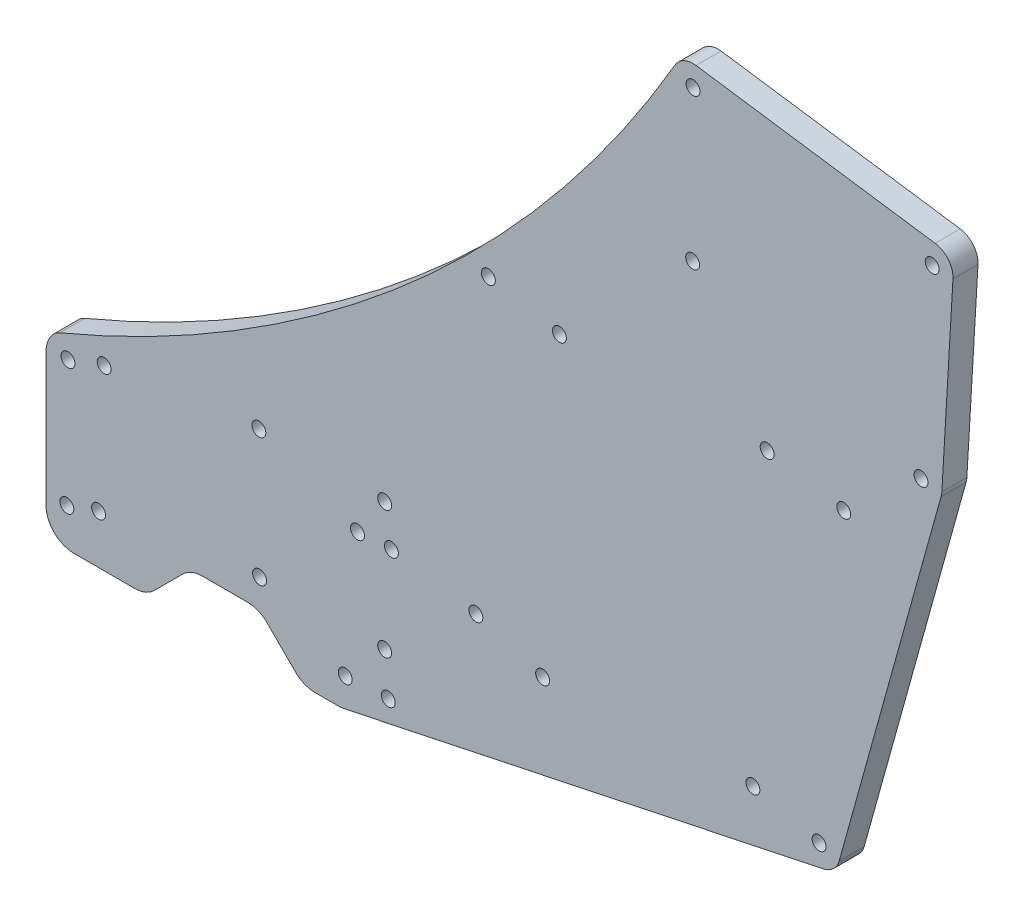
SolidWorks part; units mm, degrees
ref_plane "Front Plane" through (0, 0, 0) normal (0, 0, 1) x (1, 0, 0)
ref_plane "Top Plane" through (0, 0, 0) normal (0, 1, 0) x (1, 0, 0)
ref_plane "Right Plane" through (0, 0, 0) normal (1, 0, 0) x (0, 0, -1)
sketch "Model" plane through (0, 0, 0) normal (0, 0, 1) x (1, 0, 0)
  line L0 (-211.7059, 139.5585) -> (211.7058, 139.5585)
  line L1 (211.7058, 139.5585) -> (122.9838, -139.5584)
  line L2 (122.9838, -139.5584) -> (-211.7059, -139.5584)
  line L3 (-211.7059, -139.5584) -> (-211.7059, 139.5585)
  line L4 (-183.9889, -135.0098) -> (-175.7383, -135.0098)
  line L5 (-175.7383, -135.0098) -> (-175.7383, -139.5584)
  line L6 (-175.7383, -139.5584) -> (-183.9889, -139.5584)
  line L7 (-183.9889, -139.5584) -> (-183.9889, -135.0098)
  line L8 (5.1137, -131.3253) -> (16.7271, -131.3253)
  line L9 (16.7271, -131.3253) -> (16.7271, -139.5584)
  line L10 (16.7271, -139.5584) -> (5.1137, -139.5584)
  line L11 (5.1137, -139.5584) -> (5.1137, -131.3253)
  line L12 (-120.7856, -123.5542) -> (-97.2926, -123.5542)
  line L13 (-97.2926, -123.5542) -> (-97.2926, -126.7942)
  line L14 (-97.2926, -126.7942) -> (-120.7856, -126.7942)
  line L15 (-120.7856, -126.7942) -> (-120.7856, -123.5542)
  line L16 (-130.4136, -13.1631) -> (-127.7548, -13.1631)
  line L17 (-127.7548, -13.1631) -> (-127.7548, -110.9397)
  line L18 (-127.7548, -110.9397) -> (-130.4136, -110.9397)
  line L19 (-130.4136, -110.9397) -> (-130.4136, -13.1631)
  spline S0 degree 3 poles (121.2808, 104.4697) (121.2808, 103.8066) (121.0175, 103.1708) (120.5486, 102.7019) knots 0 0 0 0 1 1 1 1
  spline S1 degree 3 poles (120.5486, 102.7019) (120.0798, 102.2331) (119.4439, 101.9697) (118.7809, 101.9697) knots 0 0 0 0 1 1 1 1
  spline S2 degree 3 poles (118.7809, 101.9697) (117.4002, 101.9697) (116.2809, 103.089) (116.2809, 104.4697) knots 0 0 0 0 1 1 1 1
  spline S3 degree 3 poles (116.2809, 104.4697) (116.2809, 105.8504) (117.4002, 106.9696) (118.7809, 106.9696) knots 0 0 0 0 1 1 1 1
  spline S4 degree 3 poles (118.7809, 106.9696) (119.4439, 106.9696) (120.0798, 106.7062) (120.5486, 106.2374) knots 0 0 0 0 1 1 1 1
  spline S5 degree 3 poles (120.5486, 106.2374) (121.0175, 105.7686) (121.2808, 105.1327) (121.2808, 104.4697) knots 0 0 0 0 1 1 1 1
  spline S6 degree 3 poles (117.2766, 36.0936) (117.2766, 34.7129) (116.1574, 33.5937) (114.7767, 33.5937) knots 0 0 0 0 1 1 1 1
  spline S7 degree 3 poles (114.7767, 33.5937) (113.396, 33.5937) (112.2767, 34.7129) (112.2767, 36.0936) knots 0 0 0 0 1 1 1 1
  spline S8 degree 3 poles (112.2767, 36.0936) (112.2767, 37.4743) (113.396, 38.5936) (114.7767, 38.5936) knots 0 0 0 0 1 1 1 1
  spline S9 degree 3 poles (114.7767, 38.5936) (116.1574, 38.5936) (117.2766, 37.4743) (117.2766, 36.0936) knots 0 0 0 0 1 1 1 1
  spline S10 degree 3 poles (61.9275, 17.0977) (61.9275, 15.717) (60.8082, 14.5977) (59.4275, 14.5977) knots 0 0 0 0 1 1 1 1
  spline S11 degree 3 poles (59.4275, 14.5977) (58.0468, 14.5977) (56.9275, 15.717) (56.9275, 17.0977) knots 0 0 0 0 1 1 1 1
  spline S12 degree 3 poles (56.9275, 17.0977) (56.9275, 18.4784) (58.0468, 19.5976) (59.4275, 19.5976) knots 0 0 0 0 1 1 1 1
  spline S13 degree 3 poles (59.4275, 19.5976) (60.8082, 19.5976) (61.9275, 18.4784) (61.9275, 17.0977) knots 0 0 0 0 1 1 1 1
  spline S14 degree 3 poles (35.1266, 62.7496) (35.1266, 61.3689) (34.0074, 60.2496) (32.6267, 60.2496) knots 0 0 0 0 1 1 1 1
  spline S15 degree 3 poles (32.6267, 60.2496) (31.246, 60.2496) (30.1267, 61.3689) (30.1267, 62.7496) knots 0 0 0 0 1 1 1 1
  spline S16 degree 3 poles (30.1267, 62.7496) (30.1267, 64.1303) (31.246, 65.2496) (32.6267, 65.2496) knots 0 0 0 0 1 1 1 1
  spline S17 degree 3 poles (32.6267, 65.2496) (34.0074, 65.2496) (35.1266, 64.1303) (35.1266, 62.7496) knots 0 0 0 0 1 1 1 1
  spline S18 degree 3 poles (35.2798, 116.8664) (35.2798, 115.4857) (34.1605, 114.3664) (32.7798, 114.3664) knots 0 0 0 0 1 1 1 1
  spline S19 degree 3 poles (32.7798, 114.3664) (31.3991, 114.3664) (30.2798, 115.4857) (30.2798, 116.8664) knots 0 0 0 0 1 1 1 1
  spline S20 degree 3 poles (30.2798, 116.8664) (30.2798, 117.5294) (30.5432, 118.1653) (31.0121, 118.6341) knots 0 0 0 0 1 1 1 1
  spline S21 degree 3 poles (31.0121, 118.6341) (31.4809, 119.103) (32.1168, 119.3664) (32.7798, 119.3664) knots 0 0 0 0 1 1 1 1
  spline S22 degree 3 poles (32.7798, 119.3664) (33.4428, 119.3664) (34.0787, 119.103) (34.5475, 118.6341) knots 0 0 0 0 1 1 1 1
  spline S23 degree 3 poles (34.5475, 118.6341) (35.0164, 118.1653) (35.2798, 117.5294) (35.2798, 116.8664) knots 0 0 0 0 1 1 1 1
  spline S24 degree 3 poles (56.804, -89.9943) (56.804, -91.375) (55.6847, -92.4943) (54.304, -92.4943) knots 0 0 0 0 1 1 1 1
  spline S25 degree 3 poles (54.304, -92.4943) (52.9233, -92.4943) (51.804, -91.375) (51.804, -89.9943) knots 0 0 0 0 1 1 1 1
  spline S26 degree 3 poles (51.804, -89.9943) (51.804, -88.6136) (52.9233, -87.4943) (54.304, -87.4943) knots 0 0 0 0 1 1 1 1
  spline S27 degree 3 poles (54.304, -87.4943) (55.6847, -87.4943) (56.804, -88.6136) (56.804, -89.9943) knots 0 0 0 0 1 1 1 1
  spline S28 degree 3 poles (80.6115, -95.7304) (80.6115, -97.1111) (79.4922, -98.2304) (78.1115, -98.2304) knots 0 0 0 0 1 1 1 1
  spline S29 degree 3 poles (78.1115, -98.2304) (76.7308, -98.2304) (75.6115, -97.1111) (75.6115, -95.7304) knots 0 0 0 0 1 1 1 1
  spline S30 degree 3 poles (75.6115, -95.7304) (75.6115, -94.3497) (76.7308, -93.2304) (78.1115, -93.2304) knots 0 0 0 0 1 1 1 1
  spline S31 degree 3 poles (78.1115, -93.2304) (79.4922, -93.2304) (80.6115, -94.3497) (80.6115, -95.7304) knots 0 0 0 0 1 1 1 1
  spline S32 degree 3 poles (-189.541, -80.3042) (-189.541, -81.6849) (-190.6603, -82.8042) (-192.041, -82.8042) knots 0 0 0 0 1 1 1 1
  spline S33 degree 3 poles (-192.041, -82.8042) (-193.4217, -82.8042) (-194.5409, -81.6849) (-194.5409, -80.3042) knots 0 0 0 0 1 1 1 1
  spline S34 degree 3 poles (-194.5409, -80.3042) (-194.5409, -78.9235) (-193.4217, -77.8043) (-192.041, -77.8043) knots 0 0 0 0 1 1 1 1
  spline S35 degree 3 poles (-192.041, -77.8043) (-190.6603, -77.8043) (-189.541, -78.9235) (-189.541, -80.3042) knots 0 0 0 0 1 1 1 1
  spline S36 degree 3 poles (-85.4284, -81.8636) (-85.4284, -82.5266) (-85.6918, -83.1625) (-86.1606, -83.6313) knots 0 0 0 0 1 1 1 1
  spline S37 degree 3 poles (-86.1606, -83.6313) (-86.6295, -84.1001) (-87.2654, -84.3635) (-87.9284, -84.3635) knots 0 0 0 0 1 1 1 1
  spline S38 degree 3 poles (-87.9284, -84.3635) (-88.5914, -84.3635) (-89.2273, -84.1001) (-89.6961, -83.6313) knots 0 0 0 0 1 1 1 1
  spline S39 degree 3 poles (-89.6961, -83.6313) (-90.165, -83.1625) (-90.4284, -82.5266) (-90.4284, -81.8636) knots 0 0 0 0 1 1 1 1
  spline S40 degree 3 poles (-90.4284, -81.8636) (-90.4284, -80.4829) (-89.3091, -79.3636) (-87.9284, -79.3636) knots 0 0 0 0 1 1 1 1
  spline S41 degree 3 poles (-87.9284, -79.3636) (-86.5477, -79.3636) (-85.4284, -80.4829) (-85.4284, -81.8636) knots 0 0 0 0 1 1 1 1
  spline S42 degree 3 poles (-73.2184, -81.251) (-73.2184, -82.6317) (-74.3377, -83.7509) (-75.7183, -83.7509) knots 0 0 0 0 1 1 1 1
  spline S43 degree 3 poles (-75.7183, -83.7509) (-76.3814, -83.7509) (-77.0173, -83.4875) (-77.4861, -83.0187) knots 0 0 0 0 1 1 1 1
  spline S44 degree 3 poles (-77.4861, -83.0187) (-77.9549, -82.5499) (-78.2183, -81.914) (-78.2183, -81.251) knots 0 0 0 0 1 1 1 1
  spline S45 degree 3 poles (-78.2183, -81.251) (-78.2183, -80.5879) (-77.9549, -79.9521) (-77.4861, -79.4832) knots 0 0 0 0 1 1 1 1
  spline S46 degree 3 poles (-77.4861, -79.4832) (-77.0173, -79.0144) (-76.3814, -78.751) (-75.7183, -78.751) knots 0 0 0 0 1 1 1 1
  spline S47 degree 3 poles (-75.7183, -78.751) (-74.3377, -78.751) (-73.2184, -79.8703) (-73.2184, -81.251) knots 0 0 0 0 1 1 1 1
  spline S48 degree 3 poles (-42.8255, -86.1238) (-42.8255, -86.7869) (-43.0889, -87.4228) (-43.5578, -87.8916) knots 0 0 0 0 1 1 1 1
  spline S49 degree 3 poles (-43.5578, -87.8916) (-44.0266, -88.3604) (-44.6625, -88.6238) (-45.3255, -88.6238) knots 0 0 0 0 1 1 1 1
  spline S50 degree 3 poles (-45.3255, -88.6238) (-45.9885, -88.6238) (-46.6244, -88.3604) (-47.0932, -87.8916) knots 0 0 0 0 1 1 1 1
  spline S51 degree 3 poles (-47.0932, -87.8916) (-47.5621, -87.4228) (-47.8255, -86.7869) (-47.8255, -86.1238) knots 0 0 0 0 1 1 1 1
  spline S52 degree 3 poles (-47.8255, -86.1238) (-47.8255, -84.7432) (-46.7062, -83.6239) (-45.3255, -83.6239) knots 0 0 0 0 1 1 1 1
  spline S53 degree 3 poles (-45.3255, -83.6239) (-43.9448, -83.6239) (-42.8255, -84.7432) (-42.8255, -86.1238) knots 0 0 0 0 1 1 1 1
  spline S54 degree 3 poles (-18.8231, -93.7812) (-18.8231, -95.1619) (-19.9424, -96.2812) (-21.3231, -96.2812) knots 0 0 0 0 1 1 1 1
  spline S55 degree 3 poles (-21.3231, -96.2812) (-22.7038, -96.2812) (-23.823, -95.1619) (-23.823, -93.7812) knots 0 0 0 0 1 1 1 1
  spline S56 degree 3 poles (-23.823, -93.7812) (-23.823, -92.4005) (-22.7038, -91.2813) (-21.3231, -91.2813) knots 0 0 0 0 1 1 1 1
  spline S57 degree 3 poles (-21.3231, -91.2813) (-19.9424, -91.2813) (-18.8231, -92.4005) (-18.8231, -93.7812) knots 0 0 0 0 1 1 1 1
  spline S58 degree 3 poles (-38.3425, 21.163) (-38.3425, 19.7824) (-39.4618, 18.6631) (-40.8425, 18.6631) knots 0 0 0 0 1 1 1 1
  spline S59 degree 3 poles (-40.8425, 18.6631) (-42.2231, 18.6631) (-43.3424, 19.7824) (-43.3424, 21.163) knots 0 0 0 0 1 1 1 1
  spline S60 degree 3 poles (-43.3424, 21.163) (-43.3424, 22.5437) (-42.2231, 23.663) (-40.8425, 23.663) knots 0 0 0 0 1 1 1 1
  spline S61 degree 3 poles (-40.8425, 23.663) (-39.4618, 23.663) (-38.3425, 22.5437) (-38.3425, 21.163) knots 0 0 0 0 1 1 1 1
  spline S62 degree 3 poles (-12.7807, 15.9839) (-12.7807, 14.6032) (-13.9, 13.4839) (-15.2807, 13.4839) knots 0 0 0 0 1 1 1 1
  spline S63 degree 3 poles (-15.2807, 13.4839) (-16.6614, 13.4839) (-17.7807, 14.6032) (-17.7807, 15.9839) knots 0 0 0 0 1 1 1 1
  spline S64 degree 3 poles (-17.7807, 15.9839) (-17.7807, 17.3646) (-16.6614, 18.4838) (-15.2807, 18.4838) knots 0 0 0 0 1 1 1 1
  spline S65 degree 3 poles (-15.2807, 18.4838) (-13.9, 18.4838) (-12.7807, 17.3646) (-12.7807, 15.9839) knots 0 0 0 0 1 1 1 1
  spline S66 degree 3 poles (-176.5282, -75.6233) (-176.5282, -76.2863) (-176.7916, -76.9222) (-177.2604, -77.391) knots 0 0 0 0 1 1 1 1
  spline S67 degree 3 poles (-177.2604, -77.391) (-177.7293, -77.8599) (-178.3651, -78.1233) (-179.0282, -78.1233) knots 0 0 0 0 1 1 1 1
  spline S68 degree 3 poles (-179.0282, -78.1233) (-179.6912, -78.1233) (-180.3271, -77.8599) (-180.7959, -77.391) knots 0 0 0 0 1 1 1 1
  spline S69 degree 3 poles (-180.7959, -77.391) (-181.2647, -76.9222) (-181.5281, -76.2863) (-181.5281, -75.6233) knots 0 0 0 0 1 1 1 1
  spline S70 degree 3 poles (-181.5281, -75.6233) (-181.5281, -74.2426) (-180.4089, -73.1233) (-179.0282, -73.1233) knots 0 0 0 0 1 1 1 1
  spline S71 degree 3 poles (-179.0282, -73.1233) (-177.6475, -73.1233) (-176.5282, -74.2426) (-176.5282, -75.6233) knots 0 0 0 0 1 1 1 1
  spline S72 degree 3 poles (-189.9448, -125.9005) (-189.9448, -127.2812) (-191.064, -128.4004) (-192.4447, -128.4004) knots 0 0 0 0 1 1 1 1
  spline S73 degree 3 poles (-192.4447, -128.4004) (-193.8254, -128.4004) (-194.9447, -127.2812) (-194.9447, -125.9005) knots 0 0 0 0 1 1 1 1
  spline S74 degree 3 poles (-194.9447, -125.9005) (-194.9447, -124.5198) (-193.8254, -123.4005) (-192.4447, -123.4005) knots 0 0 0 0 1 1 1 1
  spline S75 degree 3 poles (-192.4447, -123.4005) (-191.064, -123.4005) (-189.9448, -124.5198) (-189.9448, -125.9005) knots 0 0 0 0 1 1 1 1
  spline S76 degree 3 poles (-178.5283, -121.9882) (-178.5283, -123.3689) (-179.6475, -124.4882) (-181.0282, -124.4882) knots 0 0 0 0 1 1 1 1
  spline S77 degree 3 poles (-181.0282, -124.4882) (-181.6913, -124.4882) (-182.3271, -124.2248) (-182.796, -123.756) knots 0 0 0 0 1 1 1 1
  spline S78 degree 3 poles (-182.796, -123.756) (-183.2648, -123.2871) (-183.5282, -122.6513) (-183.5282, -121.9882) knots 0 0 0 0 1 1 1 1
  spline S79 degree 3 poles (-183.5282, -121.9882) (-183.5282, -121.3252) (-183.2648, -120.6893) (-182.796, -120.2205) knots 0 0 0 0 1 1 1 1
  spline S80 degree 3 poles (-182.796, -120.2205) (-182.3271, -119.7516) (-181.6913, -119.4882) (-181.0282, -119.4882) knots 0 0 0 0 1 1 1 1
  spline S81 degree 3 poles (-181.0282, -119.4882) (-180.3652, -119.4882) (-179.7293, -119.7516) (-179.2605, -120.2205) knots 0 0 0 0 1 1 1 1
  spline S82 degree 3 poles (-179.2605, -120.2205) (-178.7917, -120.6893) (-178.5283, -121.3252) (-178.5283, -121.9882) knots 0 0 0 0 1 1 1 1
  spline S83 degree 3 poles (-74.3322, -128.3369) (-74.3322, -129.7176) (-75.4514, -130.8369) (-76.8321, -130.8369) knots 0 0 0 0 1 1 1 1
  spline S84 degree 3 poles (-76.8321, -130.8369) (-77.4952, -130.8369) (-78.1311, -130.5735) (-78.5999, -130.1046) knots 0 0 0 0 1 1 1 1
  spline S85 degree 3 poles (-78.5999, -130.1046) (-79.0687, -129.6358) (-79.3321, -128.9999) (-79.3321, -128.3369) knots 0 0 0 0 1 1 1 1
  spline S86 degree 3 poles (-79.3321, -128.3369) (-79.3321, -127.6739) (-79.0687, -127.038) (-78.5999, -126.5692) knots 0 0 0 0 1 1 1 1
  spline S87 degree 3 poles (-78.5999, -126.5692) (-78.1311, -126.1003) (-77.4952, -125.8369) (-76.8321, -125.8369) knots 0 0 0 0 1 1 1 1
  spline S88 degree 3 poles (-76.8321, -125.8369) (-75.4514, -125.8369) (-74.3322, -126.9562) (-74.3322, -128.3369) knots 0 0 0 0 1 1 1 1
  spline S89 degree 3 poles (-89.8001, -128.9495) (-89.8001, -129.6125) (-90.0635, -130.2484) (-90.5323, -130.7172) knots 0 0 0 0 1 1 1 1
  spline S90 degree 3 poles (-90.5323, -130.7172) (-91.0012, -131.1861) (-91.637, -131.4494) (-92.3001, -131.4494) knots 0 0 0 0 1 1 1 1
  spline S91 degree 3 poles (-92.3001, -131.4494) (-93.6808, -131.4494) (-94.8, -130.3302) (-94.8, -128.9495) knots 0 0 0 0 1 1 1 1
  spline S92 degree 3 poles (-94.8, -128.9495) (-94.8, -127.5688) (-93.6808, -126.4495) (-92.3001, -126.4495) knots 0 0 0 0 1 1 1 1
  spline S93 degree 3 poles (-92.3001, -126.4495) (-91.637, -126.4495) (-91.0012, -126.7129) (-90.5323, -127.1817) knots 0 0 0 0 1 1 1 1
  spline S94 degree 3 poles (-90.5323, -127.1817) (-90.0635, -127.6506) (-89.8001, -128.2864) (-89.8001, -128.9495) knots 0 0 0 0 1 1 1 1
  spline S95 degree 3 poles (89.4662, 12.2666) (89.4662, 10.8859) (88.3469, 9.7666) (86.9662, 9.7666) knots 0 0 0 0 1 1 1 1
  spline S96 degree 3 poles (86.9662, 9.7666) (85.5855, 9.7666) (84.4663, 10.8859) (84.4663, 12.2666) knots 0 0 0 0 1 1 1 1
  spline S97 degree 3 poles (84.4663, 12.2666) (84.4663, 13.6472) (85.5855, 14.7665) (86.9662, 14.7665) knots 0 0 0 0 1 1 1 1
  spline S98 degree 3 poles (86.9662, 14.7665) (88.3469, 14.7665) (89.4662, 13.6472) (89.4662, 12.2666) knots 0 0 0 0 1 1 1 1
sketch "Sketch2" plane through (0, 0, 0) normal (0, 0, 1) x (1, 0, 0)
  line L0 (-211.7059, -139.5584) -> (122.9838, -139.5584)
  line L18 (-211.7059, -139.5584) -> (-211.7059, 139.5585)
  line L19 (-211.7059, 139.5585) -> (211.7058, 139.5585)
  line L20 (211.7058, 139.5585) -> (122.9838, -139.5584)
  circle A0 centre (-192.4447, -125.9005) radius 2.5
  circle A1 centre (-181.0282, -121.9882) radius 2.5
  circle A2 centre (-192.041, -80.3042) radius 2.5
  circle A3 centre (-179.0282, -75.6233) radius 2.5
  circle A4 centre (-92.3001, -128.9495) radius 2.5
  circle A5 centre (-76.8321, -128.3369) radius 2.5
  circle A6 centre (-87.9284, -81.8636) radius 2.5
  circle A7 centre (-75.7183, -81.251) radius 2.5
  circle A8 centre (-45.3255, -86.1239) radius 2.5
  circle A9 centre (-21.3231, -93.7812) radius 2.5
  circle A10 centre (54.304, -89.9943) radius 2.5
  circle A11 centre (78.1115, -95.7304) radius 2.5
  circle A12 centre (114.7767, 36.0936) radius 2.5
  circle A13 centre (86.9662, 12.2666) radius 2.5
  circle A14 centre (59.4275, 17.0977) radius 2.5
  circle A15 centre (-40.8425, 21.163) radius 2.5
  circle A16 centre (-15.2807, 15.9839) radius 2.5
  circle A17 centre (32.6267, 62.7496) radius 2.5
  circle A18 centre (118.7809, 104.4697) radius 2.5
  circle A19 centre (32.7798, 116.8664) radius 2.5
extrude "Boss-Extrude1" add sketch "Sketch2" along normal blind 9
sketch "Sketch3" plane through (0, 0, 9) normal (0, 0, 1) x (1, 0, 0)
  line L0 (73.706, -139.5584) -> (151.3388, 139.5585)
  line L1 (-211.7059, -139.5584) -> (122.9838, -139.5584) construction
  line L2 (-211.7059, 139.5585) -> (211.7058, 139.5585) construction
  line L3 (-199.9447, 139.5585) -> (-199.9447, -139.5584)
  line L4 (-211.7059, -87.5749) -> (47.2794, 139.5585)
  line L5 (-211.7059, -139.5584) -> (-211.7059, 139.5585) construction
  line L6 (-211.7059, 124.3664) -> (206.8768, 124.3664)
  line L7 (211.7058, 139.5585) -> (122.9838, -139.5584) construction
  line L9 (211.7058, 139.5585) -> (-211.7059, 139.5585)
  line L10 (211.7058, 139.5585) -> (211.7058, -139.5584)
  line L11 (211.7058, -139.5584) -> (-211.7059, -139.5584)
  line L12 (-211.7059, 139.5585) -> (-211.7059, -139.5584)
  circle A0 centre (114.7767, 36.0936) radius 7.5
  circle A1 centre (78.1115, -95.7304) radius 7.5
  circle A2 centre (-192.4447, -125.9005) radius 7.5
  circle A3 centre (-192.041, -80.3042) radius 7.5
  circle A4 centre (32.7798, 116.8664) radius 7.5
  circle A5 centre (114.7767, 36.0936) radius 2.5 construction
  circle A6 centre (118.7809, 104.4697) radius 7.5
  line M29 (122.9838, -139.5584) -> (211.7058, 139.5585)
  line M30 (211.7058, 139.5585) -> (-211.7059, 139.5585)
  line M31 (-211.7059, 139.5585) -> (-211.7059, -139.5584)
  line M32 (-211.7059, -139.5584) -> (122.9838, -139.5584)
  dimension "D1" = 15
extrude "Cut-Extrude1" cut sketch "Sketch3" against normal blind 10 contours L6 L4 L3 M31 | L4 L3 M31 M32 | L6 L0 M32 M29 | L6 L3 L4 | L6 L3 M31 M30 | L3 L6 L4 M30 | L4 L6 L0 M30 | L0 L6 M29 M30 | L12 L11 L10 L9
sketch "Sketch4" plane through (0, 0, 9) normal (0, 0, 1) x (1, 0, 0)
  line L5 (-163.8851, -139.5584) -> (-147.8809, -123.5542)
  line L6 (-199.9447, -139.5584) -> (73.706, -139.5584) construction
  line L7 (-147.8809, -123.5542) -> (-123.3337, -123.5542)
  line L8 (-123.3337, -123.5542) -> (-107.3295, -139.5584)
  line L9 (-107.3295, -139.5584) -> (-163.8851, -139.5584)
  line L10 (-155.883, -131.5563) -> (-115.3316, -131.5563) construction
  line L11 (-135.6073, -123.5542) -> (-135.6073, -131.5563) construction
  line L12 (-128.1309, -123.5542) -> (-73.1309, -123.5542) construction
  line L13 (-147.8809, -91.0542) -> (-123.3337, -91.0542) construction
  line L14 (-147.8809, -85.5542) -> (-147.8809, -96.5542) construction
  line L15 (-123.3337, -72.156) -> (-123.3337, -109.9525) construction
  line L16 (-135.6073, -123.5542) -> (-135.6073, -91.0542) construction
  line L17 (-147.8809, -117.5859) -> (-147.8809, -123.5542) construction
  dimension "D1" = 45
extrude "Cut-Extrude2" cut sketch "Sketch4" against normal through all
sketch "Sketch5" plane through (0, 0, 9) normal (0, 0, 1) x (1, 0, 0)
  line L0 (-120.6309, -113.5542) -> (-125.6309, -113.5542) construction
  line L1 (-120.6309, -117.5542) -> (-120.6309, -109.5542) construction
  line L3 (-123.3809, -117.5859) -> (-123.3809, -64.5226) construction
  line L4 (-75.6309, -67.5542) -> (-80.6309, -67.5542) construction
  line L5 (-75.6309, -72.0542) -> (-75.6309, -63.0542) construction
  line L6 (-80.6309, -63.0542) -> (-80.6309, -72.0542) construction
  line L7 (-78.1309, -67.5542) -> (-123.3809, -67.5542) construction
  line L8 (-78.1309, -113.5542) -> (-78.1309, -67.5542) construction
  line L9 (-123.1309, -113.5542) -> (-78.1309, -113.5542) construction
  circle A0 centre (-123.1309, -113.5542) radius 2.5
  circle A1 centre (-78.1309, -113.5542) radius 2.5
  circle A2 centre (-123.3809, -67.5542) radius 2.5
  circle A3 centre (-78.1309, -67.5542) radius 2.5
  dimension "D1" = 5
extrude "Cut-Extrude3" cut sketch "Sketch5" against normal through all
sketch "Sketch6" plane through (0, 0, 9) normal (0, 0, 1) x (1, 0, 0)
  line L0 (-199.9447, -77.2602) -> (-199.9447, -139.5584) construction
  line L1 (-194.9336, -73.3845) -> (-199.9447, -73.3845)
  line L2 (-199.9447, -139.5584) -> (147.1133, -139.5584)
  line L3 (-199.9447, -139.5584) -> (-199.9447, 124.3664)
  line L4 (-199.9447, 124.3664) -> (147.1133, 124.3664)
  line L5 (147.1133, -139.5584) -> (147.1133, 124.3664)
  line L6 (26.2967, 120.6372) -> (26.2967, 124.3664)
  line L7 (33.8498, 124.2897) -> (119.8509, 111.8929)
  line L8 (126.2681, 104.0312) -> (122.2638, 35.6552)
  line L9 (122.2638, 35.6552) -> (147.1133, 35.6552)
  line L10 (79.656, -103.0696) -> (-93.736, -139.5584)
  line L11 (79.656, -103.0696) -> (147.1133, -103.0696)
  circle A0 centre (-192.041, -80.3042) radius 7.5
  circle A1 centre (-40.8425, 21.163) radius 7.5
  circle A3 centre (114.7767, 36.0936) radius 7.5
  circle A4 centre (32.7798, 116.8664) radius 7.5
  circle A5 centre (118.7809, 104.4697) radius 7.5
  circle A6 centre (78.1115, -95.7304) radius 7.5
  circle A7 centre (-76.8321, -128.3369) radius 7.5
  circle A8 centre (-192.4447, -125.9005) radius 7.5
  circle A9 centre (-179.0282, -75.6233) radius 7.5
  arc A10 (-194.9336, -73.3845) -> (26.2967, 120.6372) centre (-373.1679, 352.9825) ccw
  line M19 (73.706, -139.5584) -> (147.1133, 124.3664)
  line M20 (147.1133, 124.3664) -> (29.9569, 124.3664)
  line M21 (29.9569, 124.3664) -> (-199.9447, -77.2602)
extrude "Cut-Extrude5" cut sketch "Sketch6" against normal blind 10 contours L1 A10 L6 M21 | L9 L5 M19 | L11 L10 L2 M19 | A6 L11 M19 | A0 L1 M21 | L6 L4 M21 | A4 L6 M21 | A4 L4 M21 | A5 L8 L9 A4 L7 M19 M20 | A3 L9 M19
fillet "Fillet1" radius 10 7 edges at (-199.9447, -77.2602, 4.5) (-163.8851, -139.5584, 4.5) (-147.8809, -123.5542, 4.5) (-123.3337, -123.5542, 4.5) (-107.3295, -139.5584, 4.5) (-93.736, -139.5584, 4.5) (-199.9447, -139.5584, 4.5)
